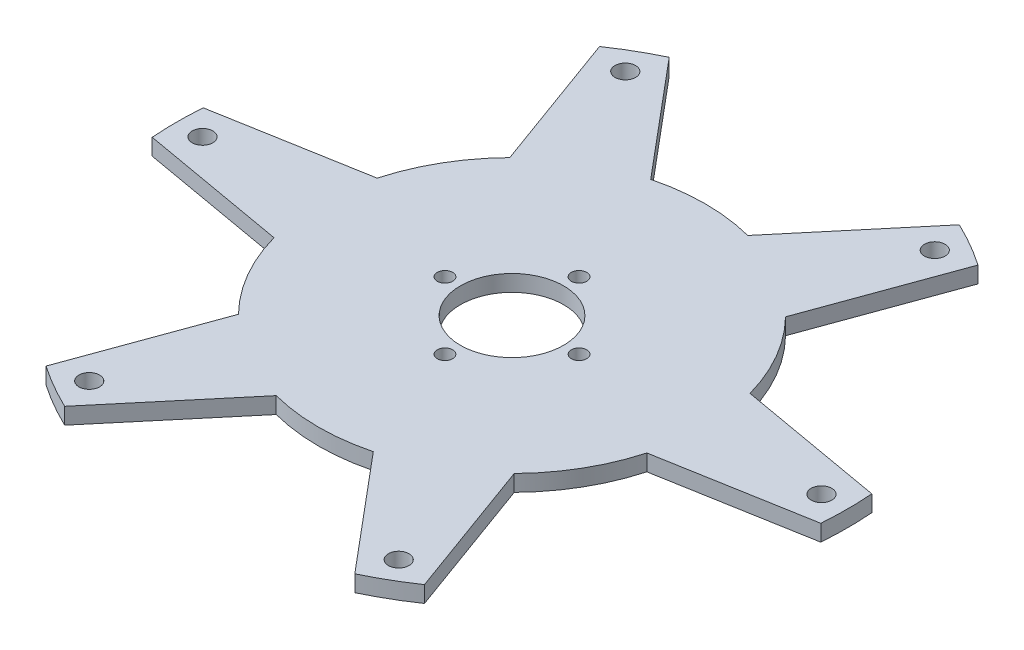
SolidWorks part; units mm, degrees
ref_plane "Front Plane" through (0, 0, 0) normal (0, 0, 1) x (1, 0, 0)
ref_plane "Top Plane" through (0, 0, 0) normal (0, 1, 0) x (1, 0, 0)
ref_plane "Right Plane" through (0, 0, 0) normal (1, 0, 0) x (0, 0, -1)
sketch "Sketch2" plane through (0, 0, 0) normal (0, 1, 0) x (1, 0, 0)
  line L0 (-55, 0) -> (-65, 0) construction
  line L1 (-36.1421, 10) -> (-64.8116, 4.9448)
  line L2 (-36.1421, -10) -> (-64.8116, -4.9448)
  line L3 (-9.4108, 36.3) -> (-28.1235, 58.6009)
  line L4 (-26.7313, 26.3) -> (-36.6881, 53.6561)
  line L5 (26.7313, 26.3) -> (36.6881, 53.6561)
  line L6 (9.4108, 36.3) -> (28.1235, 58.6009)
  line L7 (36.1421, -10) -> (64.8116, -4.9448)
  line L8 (36.1421, 10) -> (64.8116, 4.9448)
  line L9 (9.4108, -36.3) -> (28.1235, -58.6009)
  line L10 (26.7313, -26.3) -> (36.6881, -53.6561)
  line L11 (-26.7313, -26.3) -> (-36.6881, -53.6561)
  line L12 (-9.4108, -36.3) -> (-28.1235, -58.6009)
  circle A0 centre (0, 0) radius 10
  arc A1 (-64.8116, 4.9448) -> (-64.8116, -4.9448) centre (0, 0) ccw
  circle A2 centre (0, 0) radius 13 construction
  circle A3 centre (0, 13) radius 1.5
  circle A4 centre (13, 0) radius 1.5
  circle A5 centre (0, -13) radius 1.5
  circle A6 centre (-13, 0) radius 1.5
  circle A7 centre (0, 0) radius 55 construction
  circle A8 centre (-60, 0) radius 2
  circle A9 centre (-30, 51.9615) radius 2
  circle A10 centre (30, 51.9615) radius 2
  circle A11 centre (60, 0) radius 2
  circle A12 centre (30, -51.9615) radius 2
  circle A13 centre (-30, -51.9615) radius 2
  circle A14 centre (0, 0) radius 60 construction
  arc A15 (-36.1421, -10) -> (-26.7313, -26.3) centre (0, 0) ccw
  arc A16 (-28.1235, 58.6009) -> (-36.6881, 53.6561) centre (0, 0) ccw
  arc A17 (36.6881, 53.6561) -> (28.1235, 58.6009) centre (0, 0) ccw
  arc A18 (64.8116, -4.9448) -> (64.8116, 4.9448) centre (0, 0) ccw
  arc A19 (28.1235, -58.6009) -> (36.6881, -53.6561) centre (0, 0) ccw
  arc A20 (-36.6881, -53.6561) -> (-28.1235, -58.6009) centre (0, 0) ccw
  arc A21 (-9.4108, -36.3) -> (9.4108, -36.3) centre (0, 0) ccw
  arc A22 (26.7313, -26.3) -> (36.1421, -10) centre (0, 0) ccw
  arc A23 (36.1421, 10) -> (26.7313, 26.3) centre (0, 0) ccw
  arc A24 (9.4108, 36.3) -> (-9.4108, 36.3) centre (0, 0) ccw
  arc A25 (-26.7313, 26.3) -> (-36.1421, 10) centre (0, 0) ccw
  point P16 (0, 0)
  point P31 (0, 0)
  point P57 (0, 0)
  dimension "D1" = 20
  dimension "D2" = 130
  dimension "D3" = 26
  dimension "D4" = 3
  dimension "D6" = 110
  dimension "D7" = 4
  dimension "D9" = 75
  dimension "D10" = 10
  dimension "D11" = 20
  dimension "D5" = 4
  dimension "D8" = 6
  dimension "D12" = 6
extrude "Boss-Extrude1" add sketch "Sketch2" along normal blind 3.175
